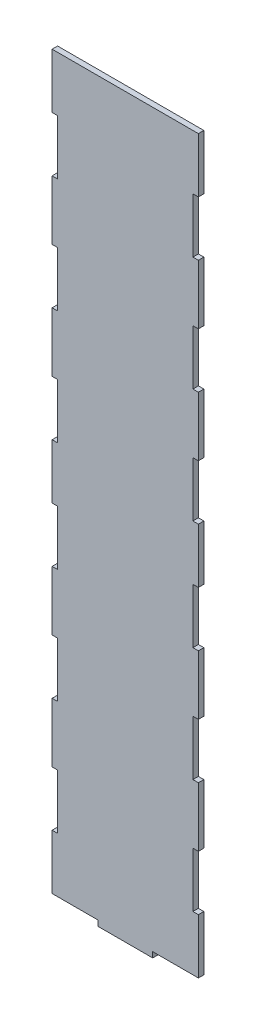
SolidWorks part; units mm, degrees
ref_plane "Plano frontal" through (0, 0, 0) normal (0, 0, 1) x (1, 0, 0)
ref_plane "Plano superior" through (0, 0, 0) normal (0, 1, 0) x (1, 0, 0)
ref_plane "Plano direito" through (0, 0, 0) normal (1, 0, 0) x (0, 0, -1)
sketch "Esboço1" plane through (0, 0, 0) normal (0, 0, 1) x (1, 0, 0)
  line L0 (0, 200) -> (0, -200) construction
  line L1 (-80, -200) -> (-55, -200)
  line L2 (-80, -200) -> (-80, 200)
  line L3 (-80, 200) -> (80, 200)
  line L4 (80, -200) -> (80, 200)
  line L5 (-80, -200) -> (80, 200) construction
  line L6 (-80, 200) -> (80, -200) construction
  line L7 (-80, 0) -> (80, 0) construction
  line L8 (-55, -200) -> (-55, -203)
  line L9 (-55, -203) -> (-25, -203)
  line L10 (-25, -203) -> (-25, -200)
  line L11 (25, -203) -> (25, -200)
  line L12 (55, -203) -> (25, -203)
  line L13 (55, -200) -> (55, -203)
  line L14 (-25, -200) -> (25, -200)
  line L15 (55, -200) -> (80, -200)
  point P0 (0, 0)
  dimension "D1" = 160
  dimension "D2" = 400
  dimension "D3" = 3
  dimension "D4" = 30
  dimension "D5" = 25
extrude "Ressalto-extrusão1" add sketch "Esboço1" along normal blind 3
sketch "Esboço2" plane through (0, 0, 3) normal (0, 0, 1) x (1, 0, 0)
  line L0 (0, 200) -> (0, 170)
  line L1 (80, 200) -> (-80, 200) construction
  line L2 (-25, -200) -> (25, -200) construction
  line L3 (80, 0) -> (-80, 0) construction
  line L4 (80, -200) -> (80, 200) construction
  line L5 (-80, 200) -> (-80, -200) construction
  line L6 (40, -203) -> (40, 200) construction
  line L7 (25, -203) -> (55, -203) construction
  line L8 (0, 170) -> (3, 170)
  line L9 (3, 170) -> (3, 140)
  line L10 (3, 140) -> (0, 140)
  line L11 (0, 107.5) -> (3, 107.5)
  line L12 (3, 107.5) -> (3, 77.5)
  line L13 (3, 77.5) -> (0, 77.5)
  line L14 (0, 45) -> (3, 45)
  line L15 (3, 45) -> (3, 15)
  line L16 (3, 15) -> (0, 15)
  line L17 (3, -140) -> (0, -140)
  line L18 (0, -170) -> (3, -170)
  line L19 (3, -170) -> (3, -140)
  line L20 (3, -77.5) -> (0, -77.5)
  line L21 (3, -107.5) -> (3, -77.5)
  line L22 (0, -107.5) -> (3, -107.5)
  line L23 (3, -15) -> (0, -15)
  line L24 (0, -45) -> (3, -45)
  line L25 (3, -45) -> (3, -15)
  line L26 (0, -170) -> (0, -200)
  line L27 (0, -107.5) -> (0, -140)
  line L28 (0, -45) -> (0, -77.5)
  line L29 (0, 15) -> (0, -15)
  line L30 (0, 77.5) -> (0, 45)
  line L31 (0, 140) -> (0, 107.5)
  line L44 (80, -200) -> (80, 200)
  line L45 (80, 200) -> (-80, 200)
  line L46 (-80, 200) -> (-80, -200)
  line L47 (-80, -200) -> (-55, -200)
  line L48 (-55, -200) -> (-55, -203)
  line L49 (-55, -203) -> (-25, -203)
  line L50 (-25, -203) -> (-25, -200)
  line L51 (-25, -200) -> (25, -200)
  line L52 (25, -200) -> (25, -203)
  line L53 (25, -203) -> (55, -203)
  line L54 (55, -203) -> (55, -200)
  line L55 (55, -200) -> (80, -200)
  line L56 (80, -200) -> (80, 200)
  line L57 (80, 200) -> (0, 200)
  line L63 (0, -200) -> (25, -200)
  line L64 (25, -200) -> (25, -203)
  line L65 (25, -203) -> (55, -203)
  line L66 (55, -203) -> (55, -200)
  line L67 (55, -200) -> (80, -200)
  dimension "D1" = 3
  dimension "D2" = 30
  dimension "D3" = 30
  dimension "D4" = 15
  dimension "D5" = 32.5
  dimension "D6" = 30
  dimension "D7" = 30
  dimension "D8" = 0
extrude "Corte-extrusão1" cut sketch "Esboço2" against normal through all flip side to cut
sketch "Esboço3" plane through (0, 0, 3) normal (0, 0, 1) x (1, 0, 0)
  line L0 (40, -203) -> (40, 200) construction
  line L1 (25, -203) -> (55, -203) construction
  line L2 (80, 200) -> (0, 200) construction
  line L3 (0, 0) -> (80, 0) construction
  line L4 (80, -200) -> (80, 200) construction
  line L5 (80, 170) -> (77, 170)
  line L6 (77, 170) -> (77, 140)
  line L7 (77, 140) -> (80, 140)
  line L8 (77, 107.5) -> (80, 107.5)
  line L9 (77, 107.5) -> (77, 77.5)
  line L10 (77, 77.5) -> (80, 77.5)
  line L11 (80, 45) -> (77, 45)
  line L12 (77, 45) -> (77, 15)
  line L13 (77, 15) -> (80, 15)
  line L14 (77, -77.5) -> (80, -77.5)
  line L15 (77, -107.5) -> (80, -107.5)
  line L16 (77, -107.5) -> (77, -77.5)
  line L17 (77, -140) -> (80, -140)
  line L18 (77, -170) -> (77, -140)
  line L19 (80, -170) -> (77, -170)
  line L20 (80, -45) -> (77, -45)
  line L21 (77, -15) -> (80, -15)
  line L22 (77, -45) -> (77, -15)
  line L23 (80, 170) -> (80, 140)
  line L24 (80, 107.5) -> (80, 77.5)
  line L25 (80, 45) -> (80, 15)
  line L26 (80, -15) -> (80, -45)
  line L27 (80, -77.5) -> (80, -107.5)
  line L28 (80, -140) -> (80, -170)
  dimension "D1" = 3
  dimension "D2" = 30
  dimension "D3" = 30
  dimension "D4" = 32.5
  dimension "D5" = 30
  dimension "D6" = 30
  dimension "D7" = 32.5
extrude "Corte-extrusão2" cut sketch "Esboço3" against normal through all
